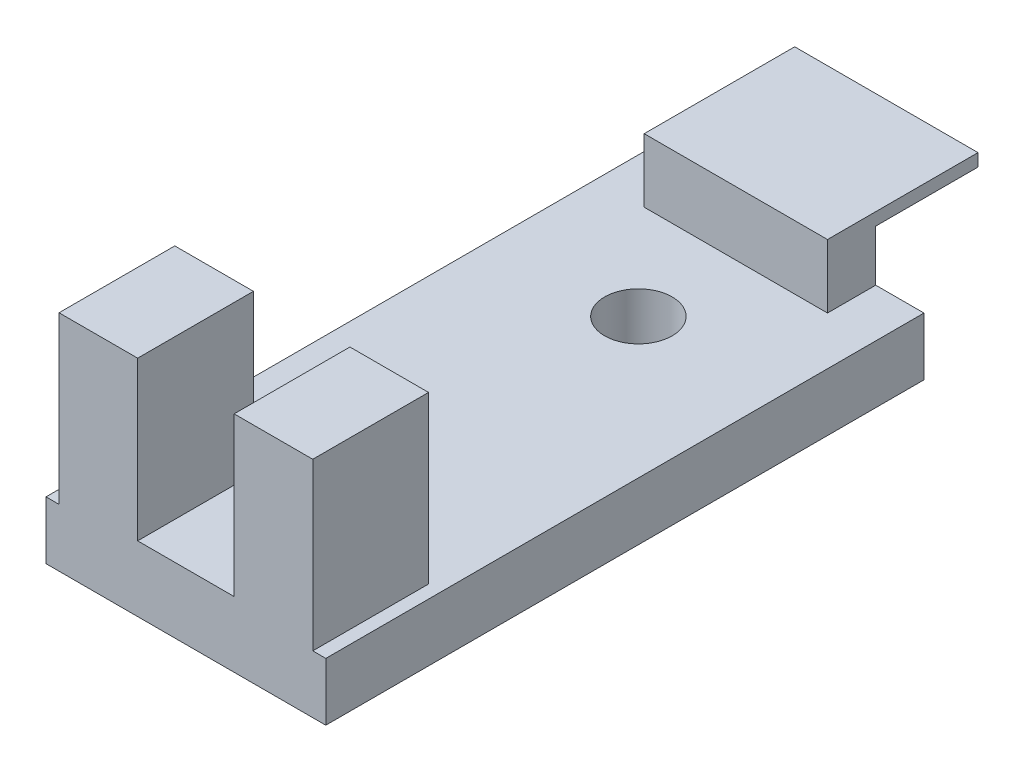
SolidWorks part; units mm, degrees
ref_plane "Front Plane" through (0, 0, 0) normal (0, 0, 1) x (1, 0, 0)
ref_plane "Top Plane" through (0, 0, 0) normal (0, 1, 0) x (1, 0, 0)
ref_plane "Right Plane" through (0, 0, 0) normal (1, 0, 0) x (0, 0, -1)
sketch "Sketch1" plane through (0, 0, 0) normal (1, 0, 0) x (0, 0, -1)
  line L0 (-15.5, 0) -> (15.5, 0)
  line L1 (15.5, 0) -> (15.5, 5.65)
  line L2 (15.5, 5.65) -> (20.8, 5.65)
  line L3 (20.8, 5.65) -> (20.8, 6.3)
  line L4 (20.8, 6.3) -> (13, 6.3)
  line L5 (13, 6.3) -> (13, 3)
  line L6 (13, 3) -> (-9.5, 3)
  line L7 (-9.5, 3) -> (-9.5, 11.6)
  line L8 (-9.5, 11.6) -> (-15.5, 11.6)
  line L9 (-15.5, 11.6) -> (-15.5, 0)
  point P10 (2.3644, 0.6509)
  dimension "D1" = 0.65
  dimension "D2" = 2.5
  dimension "D3" = 3
  dimension "D4" = 6.3
  dimension "D5" = 11.6
  dimension "D6" = 6
  dimension "D7" = 31
  dimension "D8" = 36.3
extrude "Boss-Extrude1" add sketch "Sketch1" along normal blind 7.25 and the other way blind 7.25
sketch "Sketch2" plane through (0, 3, 0) normal (0, 1, 0) x (1, 0, 0)
  line L0 (-7.25, 20.8) -> (7.25, 20.8) construction
  line L9 (-7.25, 13) -> (-4.75, 13)
  line L10 (-7.25, 13) -> (-7.25, 20.8)
  line L11 (-7.25, 20.8) -> (-4.75, 20.8)
  line L12 (-4.75, 13) -> (-4.75, 20.8)
  line L13 (-7.25, -9.5) -> (7.25, -9.5) construction
  line L14 (7.25, 13) -> (4.75, 13)
  line L15 (7.25, 13) -> (7.25, 20.8)
  line L16 (7.25, 20.8) -> (4.75, 20.8)
  line L17 (4.75, 13) -> (4.75, 20.8)
  line L18 (-6.575, -15.5) -> (6.575, -15.5)
  line L19 (-6.575, -15.5) -> (-6.575, -9.5)
  line L20 (-6.575, -9.5) -> (6.575, -9.5)
  line L21 (6.575, -15.5) -> (6.575, -9.5)
  line L22 (0, -15.5) -> (0, 0) construction
  line L23 (7.25, -9.5) -> (7.25, -15.5) construction
  line L24 (-7.25, -15.5) -> (-6.575, -15.5)
  line L25 (-7.25, -15.5) -> (-7.25, -9.5)
  line L26 (-7.25, -9.5) -> (-6.575, -9.5)
  line L27 (-6.575, -15.5) -> (-6.575, -9.5)
  line L28 (7.25, -15.5) -> (6.575, -15.5)
  line L29 (7.25, -15.5) -> (7.25, -9.5)
  line L30 (7.25, -9.5) -> (6.575, -9.5)
  line L31 (6.575, -15.5) -> (6.575, -9.5)
  line L32 (-7.25, 13) -> (-7.25, -9.5) construction
  point P26 (7.25, -15.5)
  point P34 (-7.25, -15.5)
  point P36 (-7.25, -9.5)
  line M3 (-7.25, -9.5) -> (7.25, -9.5)
  line M5 (7.25, 13) -> (-7.25, 13)
  dimension "D1" = 2.5
  dimension "D2" = 6
  dimension "D3" = 13.15
extrude "Cut-Extrude1" cut sketch "Sketch2" along normal through all contours L25 L24 L19 M3 | L28 L29 L21 M3 | L17 L15 L16 M5 | L12 L11 L10 M5 region at (-6, 3, -16.9) region at (6, 3, -16.9) region at (-6.9125, 3, 12.5) region at (6.9125, 3, 12.5)
sketch "Sketch3" plane through (0, 11.6, 0) normal (0, 1, 0) x (1, 0, 0)
  line L0 (-6.575, -9.5) -> (6.575, -9.5) construction
  line L1 (-2.5, -9.5) -> (2.5, -9.5)
  line L2 (-2.5, -9.5) -> (-2.5, -15.5)
  line L3 (-2.5, -15.5) -> (2.5, -15.5)
  line L4 (2.5, -9.5) -> (2.5, -15.5)
  line L5 (-6.575, -15.5) -> (6.575, -15.5) construction
  line L6 (0, -15.5) -> (0, 0) construction
  dimension "D1" = 5
extrude "Cut-Extrude2" cut sketch "Sketch3" against normal blind 8.2
sketch "Sketch4" plane through (0, 3, 0) normal (0, 1, 0) x (1, 0, 0)
  line L0 (0, 7.95) -> (0, 6.2) construction
  line L1 (0, 6.2) -> (0, -15.5) construction
  line L2 (-2.5, -15.5) -> (2.5, -15.5) construction
  circle A0 centre (0, 7.95) radius 1.75
  dimension "D2" = 3.5
  dimension "D1" = 21.7
extrude "Cut-Extrude3" cut sketch "Sketch4" against normal through all
